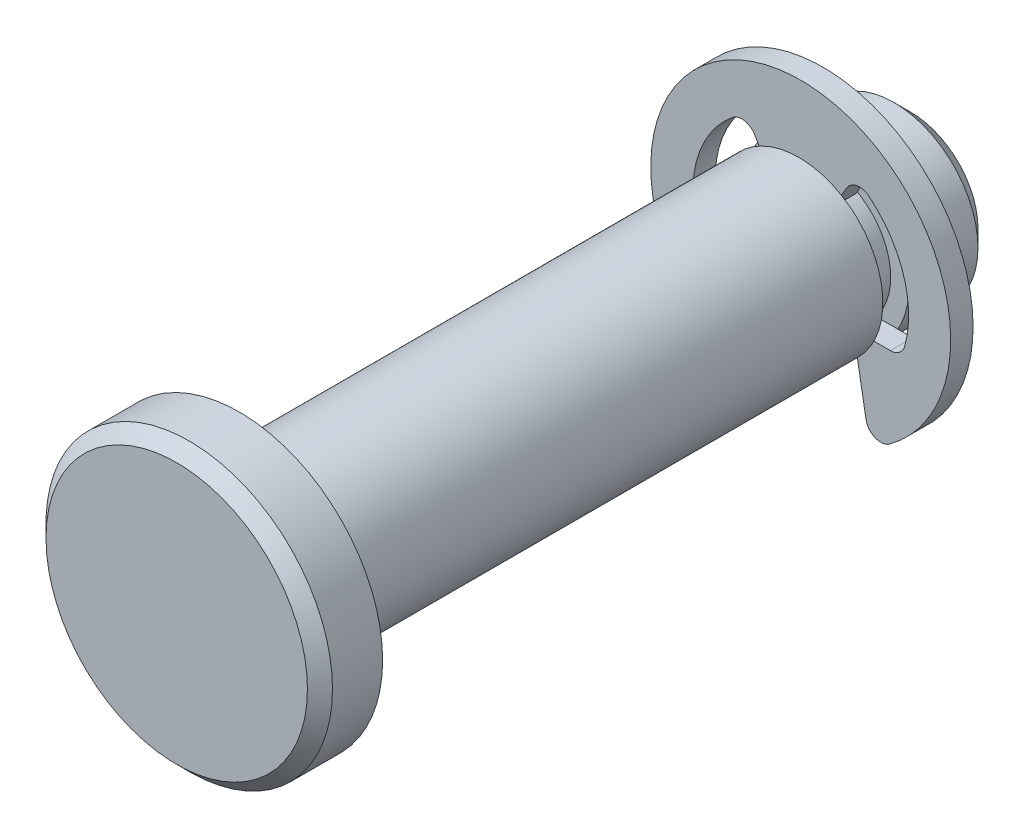
SolidWorks part; units mm, degrees
ref_plane "Front" through (0, 0, 0) normal (0, 0, 1) x (1, 0, 0)
ref_plane "Top" through (0, 0, 0) normal (0, 1, 0) x (1, 0, 0)
ref_plane "Right" through (0, 0, 0) normal (1, 0, 0) x (0, 0, -1)
sketch "Sketch2" plane through (0, 0, 0) normal (0, 0, 1) x (1, 0, 0)
  circle A0 centre (0, 0) radius 2.3813
  point P3 (0, 2.3813)
  point P4 (0, -2.3813)
  dimension "dia" = 4.7625
extrude "Extrude1" add sketch "Sketch2" along normal mid plane 19.05
sketch "Sketch3" plane through (0, 0, 0) normal (1, 0, 0) x (0, 0, -1)
  line L0 (9.525, 2.3813) -> (-9.525, 2.3813) construction
  line L1 (6.35, 2.3813) -> (7.0866, 2.3813)
  line L2 (6.35, 2.3813) -> (6.35, 1.8669)
  line L3 (6.35, 1.8669) -> (7.0866, 1.8669)
  line L4 (7.0866, 2.3813) -> (7.0866, 1.8669)
  line L5 (-9.525, 2.3813) -> (-9.525, -2.3813) construction
  line L10 (7.0866, 1.8669) -> (7.0866, -1.8669) construction
  point P11 (7.0866, 0)
  point P14 (6.7183, 2.3813)
  dimension "groove wd" = 0.7366
  dimension "groove dia" = 3.7338
  dimension "usable lg" = 15.875
revolve "Cut-Revolve1" cut sketch "Sketch3" angle 360 about axis through (0, 0, 9.525) along (0, 0, -1)
sketch "Sketch8" plane through (0, 0, 9.525) normal (0, 0, 1) x (1, 0, 0)
  circle A0 centre (0, 0) radius 4.064
  dimension "head dia" = 8.128
extrude "Extrude6" add sketch "Sketch8" along normal blind 1.778
chamfer "Chamfer2" distance 0.3556 angle 45 1 edges at (4.064, 0, 11.303)
ref_plane "Plane1" through (0, 0, -6.7183) normal (0, 0, 1) x (1, 0, 0)
sketch "Sketch4" plane through (0, 0, -6.7183) normal (0, 0, 1) x (1, 0, 0)
  line L0 (0, 1.8669) -> (0, -1.8669) construction
  circle A0 centre (0, 0) radius 4.2545
  circle A1 centre (0, 0) radius 1.8669
  dimension "ring dia" = 8.509
extrude "Extrude2" add sketch "Sketch4" along normal mid plane 0.635 separate body
sketch "Sketch5" plane through (0, 0, 0) normal (0, 0, 1) x (1, 0, 0)
  line L0 (0, 4.2545) -> (0, 1.8669) construction
  line L1 (-1.5304, 2.6506) -> (0, 0)
  line L2 (-2.8484, -1.1201) -> (-1.4935, -1.1201)
  line L3 (0, 0) -> (1.5304, 2.6506)
  line L4 (-1.4935, -1.1201) -> (-1.9617, -3.7753)
  line L5 (1.4935, -1.1201) -> (1.9617, -3.7753)
  line L6 (1.4935, -1.1201) -> (2.8484, -1.1201)
  arc A0 (-1.5304, 2.6506) -> (-2.8484, -1.1201) centre (0, 0) ccw
  circle A1 centre (0, 0) radius 4.2545 construction
  circle A2 centre (0, 0) radius 1.8669 construction
  arc A3 (2.8484, -1.1201) -> (1.5304, 2.6506) centre (0, 0) ccw
  arc A4 (-1.9617, -3.7753) -> (1.9617, -3.7753) centre (0, 0) ccw
  circle A5 centre (0, 0) radius 1.8669 construction
  point P10 (0, 3.0607)
  dimension "D1" = 30
  dimension "D2" = 10
  dimension "D3" = 1.1201
extrude "Extrude4" cut sketch "Sketch5" against normal through all
sketch "Sketch6" plane through (0, 0, -6.4008) normal (0, 0, 1) x (1, 0, 0)
  line L0 (-0.9335, 1.6168) -> (0.9335, 1.6168)
  circle A0 centre (0, 0) radius 1.8669 construction
  arc A1 (0.9335, 1.6168) -> (-0.9335, 1.6168) centre (0, 0) ccw
extrude "Extrude5" add sketch "Sketch6" against normal up to surface (0.635 mm away) up to face at (0, 0.5273, -7.0358)
fillet "Fillet1" radius 0.4254 6 edges at (1.9617, -3.7753, -6.7183) (-1.9617, -3.7753, -6.7183) (2.8484, -1.1201, -6.7183) (1.5304, 2.6506, -6.7183) (-1.5304, 2.6506, -6.7183) (-2.8484, -1.1201, -6.7183)
chamfer "Chamfer1" distance 0.4763 angle 45 1 edges at (2.3813, 0, -9.525)
sketch "Sketch7" plane through (0, 0, 0) normal (1, 0, 0) x (0, 0, -1)
  line L0 (7.0358, 4.2545) -> (6.4008, 4.2545) construction
  line L1 (9.525, -2.3813) -> (9.525, 2.3813) construction
  line L2 (6.4008, -3.5079) -> (7.0358, -3.5079) construction
  line L3 (-11.303, 3.7084) -> (-11.303, -3.7084) construction
  point P0 (7.0866, -3.5079)
  point P1 (9.525, 2.3813)
  point P2 (-11.303, 4.064)
  point P6 (6.35, 4.2545)
  point P7 (9.525, -2.3813)
  point P12 (-9.525, 4.064)
  point P16 (6.35, -3.5079)
equation "\"D1@Chamfer1\" = \"dia@Sketch2\" * .1"
equation "\"D1@Fillet1\" = \"ring dia@Sketch4\" * .05"
equation "\"D3@Sketch5\" = \"groove dia@Sketch3\" * .3"
equation "\"D1@Chamfer2\" = \"head ht@Extrude6\" * .2"
